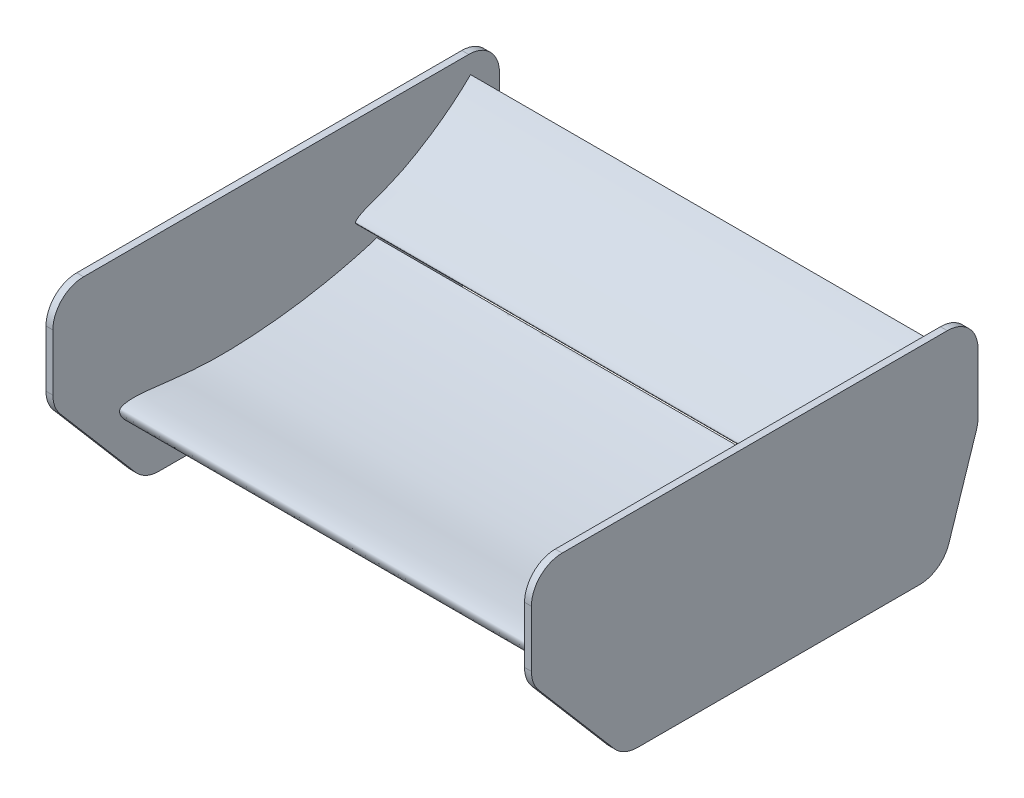
SolidWorks part; units mm, degrees
ref_plane "Front Plane" through (0, 0, 0) normal (0, 0, 1) x (1, 0, 0)
ref_plane "Top Plane" through (0, 0, 0) normal (0, 1, 0) x (1, 0, 0)
ref_plane "Right Plane" through (0, 0, 0) normal (1, 0, 0) x (0, 0, -1)
ref_plane "Soft Top Limit" through (0, 1174.6, 0) normal (0, 1, 0) x (1, 0, 0)
ref_plane "Soft Rear Limit" through (0, 0, -1192.975) normal (0, 0, 1) x (1, 0, 0)
ref_plane "Soft Right Limit" through (-501.65, 0, 0) normal (1, 0, 0) x (0, 0, -1)
ref_plane "Soft Left Limit" through (501.65, 0, 0) normal (1, 0, 0) x (0, 0, -1)
ref_plane "Soft Front Limit" through (0, 0, -165.1) normal (0, 0, 1) x (1, 0, 0)
ref_plane "Slant Limit" through (0, 528.6251, -619.2711) normal (0, -0.6492, 0.7606) x (1, 0, 0)
ref_plane "Bottom" through (0, 476.25, 0) normal (0, 1, 0) x (1, 0, 0)
ref_plane "Midplane" through (0, 0, 0) normal (1, 0, 0) x (0, 0, -1)
curve "Imported Airfoil Curve"
  spline degree 3 poles (0, 2520.0207, 6.126) (0, 2544.889, -1.81) (0, 2521.8965, 7.8839) (0, 2505.3253, 17.7145) (0, 2467.7144, 38.5723) (0, 2424.2142, 62.3813) (0, 2368.0949, 87.8078) (0, 2301.3729, 113.3478) (0, 2223.8362, 140.5377) (0, 2136.6129, 169.2441) (0, 2040.932, 199.097) (0, 1938.2341, 229.6055) (0, 1829.9414, 260.0781) (0, 1717.5266, 289.8586) (0, 1602.4273, 318.1375) (0, 1486.0259, 343.9752) (0, 1369.6902, 366.5754) (0, 1254.3666, 384.7865) (0, 1140.5393, 397.0034) (0, 1028.6357, 403.0127) (0, 919.0585, 402.9406) (0, 812.3986, 397.0375) (0, 709.2785, 385.5985) (0, 610.4299, 369.039) (0, 516.5862, 348.1086) (0, 428.5874, 323.3415) (0, 347.2653, 295.2055) (0, 273.332, 264.2656) (0, 207.4209, 231.0894) (0, 150.0337, 196.3024) (0, 101.596, 160.572) (0, 62.3674, 124.65) (0, 32.4977, 89.3959) (0, 12.0597, 55.6746) (0, 1.683, 26.6201) (0, -0.5567, 6.5526) (0, 0.5894, -3.9947) (0, 1.6947, -9.1451) (0, 2.8711, -12.4915) (0, 3.9449, -14.9776) (0, 4.8993, -16.669) (0, 5.9763, -18.2433) (0, 7.3264, -19.6365) (0, 8.8595, -20.9434) (0, 11.1868, -22.7306) (0, 14.6073, -24.7406) (0, 20.085, -27.4067) (0, 26.8353, -29.9257) (0, 44.6446, -35.1819) (0, 77.8093, -38.8998) (0, 130.2841, -38.2927) (0, 196.3018, -31.4611) (0, 276.2192, -18.4434) (0, 370.8288, 0.8611) (0, 480.7331, 24.811) (0, 605.9792, 50.0099) (0, 745.0759, 74.1542) (0, 895.4497, 95.0846) (0, 1053.6786, 110.004) (0, 1215.6439, 118.3392) (0, 1377.6893, 121.6348) (0, 1537.1174, 120.5125) (0, 1691.5141, 115.2051) (0, 1838.3121, 105.7388) (0, 1975.028, 93.0069) (0, 2099.5942, 78.4581) (0, 2210.5746, 63.1262) (0, 2306.3634, 48.0168) (0, 2387.2069, 33.7158) (0, 2449.0745, 22.0129) (0, 2499.1865, 10.4993) (0, 2520.0207, 6.126) (0, 2544.889, -1.81) (0, 2521.8965, 7.8839) knots -0.016237 -0.007308 -0.001841 0 0.001813 0.006911 0.014576 0.024172 0.035572 0.049013 0.064513 0.081849 0.100772 0.120997 0.142228 0.164173 0.186537 0.209023 0.231367 0.25332 0.274804 0.295858 0.316449 0.336531 0.356033 0.374893 0.39299 0.410197 0.426388 0.441459 0.455334 0.467938 0.479236 0.489204 0.497851 0.505194 0.511308 0.515097 0.516441 0.517273 0.51806 0.518436 0.518797 0.519154 0.519508 0.519887 0.520289 0.52116 0.522116 0.52372 0.525214 0.532575 0.542381 0.554776 0.569931 0.588005 0.609188 0.633329 0.660001 0.688743 0.718873 0.749543 0.780127 0.810209 0.839387 0.867183 0.893104 0.91676 0.937874 0.956199 0.971544 0.983763 0.992692 0.998159 1 1.001813 1.006911 1.014576 periodic
sketch "Airfoils Sketch" plane through (0, 0, 0) normal (1, 0, 0) x (0, 0, -1)
  line L0 (165.1, 1174.6) -> (165.1, 1060.6753) construction
  line L1 (165.1, 1060.6753) -> (663.9798, 476.25) construction
  line L2 (663.9798, 476.25) -> (1192.975, 476.25) construction
  line L3 (1192.975, 476.25) -> (1192.975, 1174.6) construction
  line L4 (1192.975, 1174.6) -> (165.1, 1174.6) construction
  line L5 (509.9361, 1174.6) -> (-509.9361, 1174.6) construction
  line L6 (165.1, 67.0076) -> (165.1, -67.0076) construction
  line L7 (364.7288, 826.8151) -> (873.8134, 230.4351) construction
  line L8 (279.3831, 476.25) -> (-279.3831, 476.25) construction
  line L9 (1192.975, 353.2696) -> (1192.975, -353.2696) construction
  line L10 (414.7055, 818.0274) -> (401.202, 972.3726) construction
  line L11 (945.202, 874.5029) -> (933.446, 1008.8748) construction
  line L12 (939.324, 941.6889) -> (407.9538, 895.2) construction
  line L13 (306.3538, 895.2) -> (1192.975, 895.2) construction
  line L14 (866.0383, 1036.8746) -> (926.5682, 940.0065) construction
  line L15 (1102.685, 1185.4108) -> (1163.8108, 1087.5892) construction
  line L16 (1133.2479, 1136.5) -> (896.3033, 988.4406) construction
  line L21 (176.2614, 1047.6) -> (1192.975, 1047.6) construction
  spline S0 degree 3 poles (935.2529, 940.0507) (940.3147, 942.1548) (935.6767, 939.7163) (932.3848, 937.3638) (924.8872, 932.3286) (916.21, 926.5709) (904.9213, 920.2497) (891.4161, 913.7156) (875.6775, 906.6433) (857.9391, 899.0809) (838.4515, 891.1278) (817.5075, 882.9123) (795.3921, 874.6046) (772.4019, 866.3681) (748.8232, 858.3979) (724.9284, 850.9153) (700.9897, 844.1113) (677.1845, 838.2437) (653.5854, 833.657) (630.2782, 830.4035) (607.3492, 828.4639) (584.9266, 827.7965) (563.1459, 828.3505) (542.1676, 830.0521) (522.1586, 832.7575) (503.3041, 836.37) (485.7865, 840.8065) (469.765, 845.9615) (455.382, 851.7275) (442.7539, 857.9825) (431.9816, 864.5947) (423.1327, 871.4111) (416.2539, 878.2548) (411.376, 884.946) (408.6865, 890.8402) (407.8599, 894.9991) (407.9116, 897.2265) (408.051, 898.3239) (408.2374, 899.0451) (408.4178, 899.5844) (408.5873, 899.9553) (408.7846, 900.3039) (409.0422, 900.6195) (409.3397, 900.9203) (409.7947, 901.3358) (410.4746, 901.8174) (411.5732, 902.4729) (412.9407, 903.1204) (416.5733, 904.5379) (423.4463, 905.9074) (434.4368, 906.7165) (448.3721, 906.4646) (465.3261, 905.1664) (485.4664, 902.8148) (508.8897, 899.7641) (535.5455, 896.7257) (565.0805, 894.155) (596.9177, 892.4579) (630.2914, 892.1587) (664.3294, 893.3038) (698.2942, 895.5048) (731.6326, 898.5836) (763.8436, 902.4482) (794.3904, 907.0475) (822.7695, 912.1503) (848.5739, 917.4165) (871.5218, 922.6042) (891.2949, 927.4743) (907.9553, 931.9087) (920.6916, 935.461) (930.9716, 938.764) (935.2529, 940.0507) (940.3147, 942.1548) (935.6767, 939.7163) knots -0.016237 -0.007308 -0.001841 0 0.001813 0.006911 0.014576 0.024172 0.035572 0.049013 0.064513 0.081849 0.100772 0.120997 0.142228 0.164173 0.186537 0.209023 0.231367 0.25332 0.274804 0.295858 0.316449 0.336531 0.356033 0.374893 0.39299 0.410197 0.426388 0.441459 0.455334 0.467938 0.479236 0.489204 0.497851 0.505194 0.511308 0.515097 0.516441 0.517273 0.51806 0.518436 0.518797 0.519154 0.519508 0.519887 0.520289 0.52116 0.522116 0.52372 0.525214 0.532575 0.542381 0.554776 0.569931 0.588005 0.609188 0.633329 0.660001 0.688743 0.718873 0.749543 0.780127 0.810209 0.839387 0.867183 0.893104 0.91676 0.937874 0.956199 0.971544 0.983763 0.992692 0.998159 1 1.001813 1.006911 1.014576 only from (939.324, 941.6889) to (939.324, 941.6889)
  spline S1 degree 3 poles (1131.7374, 1134.7673) (1133.5995, 1136.953) (1132.0147, 1134.712) (1131.0377, 1132.8312) (1128.7359, 1128.6983) (1126.0553, 1123.9476) (1122.2899, 1118.3128) (1117.5406, 1112.0516) (1111.8769, 1105.0082) (1105.3965, 1097.2604) (1098.1926, 1088.9143) (1090.3713, 1080.0994) (1082.0253, 1070.9629) (1073.254, 1061.6516) (1064.1447, 1052.3247) (1054.7721, 1043.1501) (1045.2175, 1034.2818) (1035.5025, 1025.8823) (1025.5791, 1018.1297) (1015.4749, 1011.0686) (1005.2348, 1004.7108) (994.9285, 999.0671) (984.6313, 994.1461) (974.4357, 989.9515) (964.4538, 986.456) (954.795, 983.6583) (945.5642, 981.5631) (936.8608, 980.159) (928.7768, 979.4298) (921.3956, 979.3461) (914.7955, 979.8704) (909.0446, 980.9475) (904.2067, 982.5058) (900.3389, 984.4687) (897.682, 986.58) (896.3072, 988.3245) (895.8017, 989.3763) (895.6058, 989.9216) (895.5213, 990.3026) (895.4772, 990.5972) (895.4681, 990.8106) (895.4773, 991.0202) (895.5225, 991.2288) (895.5898, 991.4399) (895.7034, 991.742) (895.9061, 992.1285) (896.263, 992.6957) (896.7472, 993.3231) (898.1055, 994.8485) (900.9876, 997.1221) (905.9247, 1000.1133) (912.4884, 1003.3096) (920.7099, 1006.7355) (930.6689, 1010.4274) (942.3265, 1014.5737) (955.4898, 1019.4945) (969.8856, 1025.3183) (985.1482, 1032.0973) (1000.7954, 1039.894) (1016.4092, 1048.5229) (1031.7378, 1057.6271) (1046.5653, 1066.992) (1060.6797, 1076.4556) (1073.8427, 1085.8664) (1085.8742, 1094.9966) (1096.6653, 1103.5909) (1106.1418, 1111.4691) (1114.2121, 1118.4443) (1120.9333, 1124.4758) (1126.0328, 1129.1625) (1130.0452, 1133.1487) (1131.7374, 1134.7673) (1133.5995, 1136.953) (1132.0147, 1134.712) knots -0.016237 -0.007308 -0.001841 0 0.001813 0.006911 0.014576 0.024172 0.035572 0.049013 0.064513 0.081849 0.100772 0.120997 0.142228 0.164173 0.186537 0.209023 0.231367 0.25332 0.274804 0.295858 0.316449 0.336531 0.356033 0.374893 0.39299 0.410197 0.426388 0.441459 0.455334 0.467938 0.479236 0.489204 0.497851 0.505194 0.511308 0.515097 0.516441 0.517273 0.51806 0.518436 0.518797 0.519154 0.519508 0.519887 0.520289 0.52116 0.522116 0.52372 0.525214 0.532575 0.542381 0.554776 0.569931 0.588005 0.609188 0.633329 0.660001 0.688743 0.718873 0.749543 0.780127 0.810209 0.839387 0.867183 0.893104 0.91676 0.937874 0.956199 0.971544 0.983763 0.992692 0.998159 1 1.001813 1.006911 1.014576 only from (1133.2479, 1136.5) to (1133.2479, 1136.5)
  dimension "D1" = 533.4
  dimension "D2" = 279.4
  dimension "D3" = 5
  dimension "D4" = 101.6
  dimension "D5" = 279.4
  dimension "D6" = 38.1
  dimension "D7" = 32
extrude "Extruded Airfoils" add sketch "Airfoils Sketch" along normal offset from surface (487.45 mm away) 14.2 up to plane "Soft Left Limit"
sketch "Endplate Sketch" plane through (501.65, 0, 0) normal (1, 0, 0) x (0, 0, -1)
  line L6 (333.4477, 1174.6) -> (1129.475, 1174.6)
  line L7 (1192.975, 1174.6) -> (165.1, 1174.6) construction
  line L8 (1192.975, 1111.1) -> (1192.975, 986.6717)
  line L9 (1192.975, 476.25) -> (1192.975, 1174.6) construction
  line L11 (1189.8464, 966.9854) -> (1132.8969, 792.34)
  line L12 (1072.5255, 748.5263) -> (489.1772, 748.5263)
  line L19 (440.8805, 770.7991) -> (285.151, 953.2323)
  line L26 (269.9477, 994.4595) -> (269.9477, 1111.1)
  line L28 (165.1, 1060.6753) -> (663.9798, 476.25) construction
  arc A12 (1129.475, 1174.6) -> (1192.975, 1111.1) centre (1129.475, 1111.1) cw
  arc A13 (1192.975, 986.6717) -> (1189.8464, 966.9854) centre (1129.475, 986.6717) cw
  arc A14 (1132.8969, 792.34) -> (1072.5255, 748.5263) centre (1072.5255, 812.0263) cw
  arc A15 (489.1772, 748.5263) -> (440.8805, 770.7991) centre (489.1772, 812.0263) cw
  arc A16 (285.151, 953.2323) -> (269.9477, 994.4595) centre (333.4477, 994.4595) cw
  arc A17 (333.4477, 1174.6) -> (269.9477, 1111.1) centre (333.4477, 1111.1) ccw
  point P16 (1192.975, 1174.6)
  point P19 (1192.975, 976.5799)
  point P29 (269.9477, 1174.6)
  dimension "D1" = 63.5
extrude "Extruded Endplate" add sketch "Endplate Sketch" against normal up to surface (14.2 mm away)
mirror "Mirror" about plane through (0, 0, 0) normal (1, 0, 0) of bodies 106
